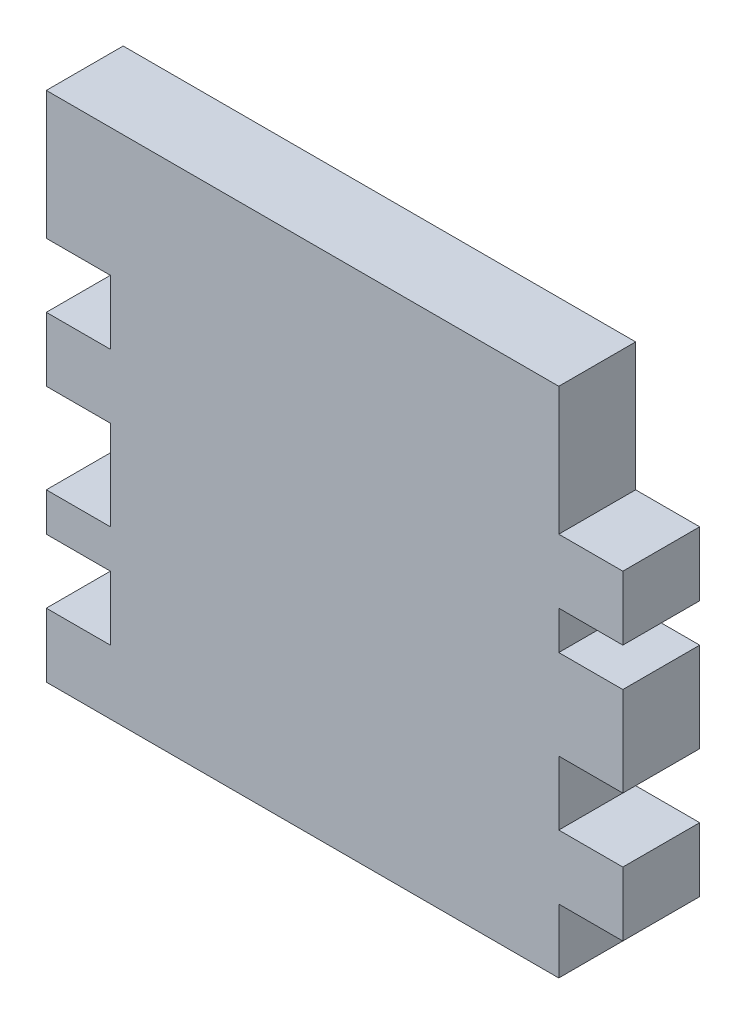
SolidWorks part; units mm, degrees
ref_plane "Front Plane" through (0, 0, 0) normal (0, 0, 1) x (1, 0, 0)
ref_plane "Top Plane" through (0, 0, 0) normal (0, 1, 0) x (1, 0, 0)
ref_plane "Right Plane" through (0, 0, 0) normal (1, 0, 0) x (0, 0, -1)
sketch "Sketch1" plane through (0, 0, 0) normal (0, 0, 1) x (1, 0, 0)
  line L1 (-18.4337, 17.4849) -> (26.5663, 17.4849)
  line L2 (-18.4337, 17.4849) -> (-18.4337, -22.5151)
  line L3 (-18.4337, -22.5151) -> (26.5663, -22.5151)
  line L4 (26.5663, 17.4849) -> (26.5663, -22.5151)
  dimension "D1" = 45
  dimension "D2" = 40
extrude "Boss-Extrude1" add sketch "Sketch1" along normal blind 6 contours L2 L1 L4 L3
sketch "Sketch2" plane through (0, 0, 6) normal (0, 0, 1) x (1, 0, 0)
  line L0 (-18.4337, 17.4849) -> (-18.4337, -22.5151) construction
  line L1 (-18.4337, 7.4849) -> (-13.4337, 7.4849)
  line L2 (-18.4337, 7.4849) -> (-18.4337, 2.4849)
  line L3 (-18.4337, 2.4849) -> (-13.4337, 2.4849)
  line L4 (-13.4337, 7.4849) -> (-13.4337, 2.4849)
  line L5 (-18.4337, 17.4849) -> (26.5663, 17.4849) construction
  line L6 (-18.4337, -2.5151) -> (-13.4337, -2.5151)
  line L7 (-18.4337, -2.5151) -> (-18.4337, -9.5151)
  line L8 (-18.4337, -9.5151) -> (-13.4337, -9.5151)
  line L9 (-13.4337, -2.5151) -> (-13.4337, -9.5151)
  line L10 (-18.4337, -12.5151) -> (-13.4337, -12.5151)
  line L11 (-18.4337, -12.5151) -> (-18.4337, -17.5151)
  line L12 (-18.4337, -17.5151) -> (-13.4337, -17.5151)
  line L13 (-13.4337, -12.5151) -> (-13.4337, -17.5151)
  line L14 (-18.4337, -22.5151) -> (26.5663, -22.5151) construction
  dimension "D1" = 5
  dimension "D2" = 5
  dimension "D3" = 5
  dimension "D4" = 5
  dimension "D5" = 10
  dimension "D6" = 5
  dimension "D7" = 5
  dimension "D8" = 5
  dimension "D9" = 7
extrude "Cut-Extrude1" cut sketch "Sketch2" against normal blind 6 contours L2 L1 L4 L3 | L7 L6 L9 L8 | L11 L10 L13 L12
sketch "Sketch3" plane through (0, 0, 6) normal (0, 0, 1) x (1, 0, 0)
  line L0 (26.5663, 17.4849) -> (26.5663, -22.5151) construction
  line L1 (21.5663, 2.4849) -> (26.5663, 2.4849)
  line L2 (21.5663, 2.4849) -> (21.5663, 7.4849)
  line L3 (21.5663, 7.4849) -> (26.5663, 7.4849)
  line L4 (26.5663, 2.4849) -> (26.5663, 7.4849)
  line L6 (26.5663, -0.5151) -> (21.5663, -0.5151)
  line L7 (26.5663, -0.5151) -> (26.5663, -7.5151)
  line L8 (26.5663, -7.5151) -> (21.5663, -7.5151)
  line L9 (21.5663, -0.5151) -> (21.5663, -7.5151)
  line L10 (26.5663, -12.5151) -> (21.5663, -12.5151)
  line L11 (26.5663, -12.5151) -> (26.5663, -17.5151)
  line L12 (26.5663, -17.5151) -> (21.5663, -17.5151)
  line L13 (21.5663, -12.5151) -> (21.5663, -17.5151)
  line L16 (21.5663, 7.4849) -> (26.5663, 7.4849)
  line L17 (21.5663, 7.4849) -> (21.5663, 17.4849)
  line L18 (21.5663, 17.4849) -> (26.5663, 17.4849)
  line L19 (26.5663, 7.4849) -> (26.5663, 17.4849)
  line L20 (21.5663, -0.5151) -> (26.5663, -0.5151)
  line L21 (21.5663, -0.5151) -> (21.5663, 2.4849)
  line L22 (21.5663, 2.4849) -> (26.5663, 2.4849)
  line L23 (26.5663, -0.5151) -> (26.5663, 2.4849)
  line L24 (21.5663, -12.5151) -> (26.5663, -12.5151)
  line L25 (21.5663, -12.5151) -> (21.5663, -7.5151)
  line L26 (21.5663, -7.5151) -> (26.5663, -7.5151)
  line L27 (26.5663, -12.5151) -> (26.5663, -7.5151)
  line L28 (21.5663, -17.5151) -> (26.5663, -17.5151)
  line L29 (21.5663, -17.5151) -> (21.5663, -22.5151)
  line L30 (21.5663, -22.5151) -> (26.5663, -22.5151)
  line L31 (26.5663, -17.5151) -> (26.5663, -22.5151)
  line M19 (-18.4337, -22.5151) -> (26.5663, -22.5151)
  line M20 (26.5663, -22.5151) -> (26.5663, 17.4849)
  line M21 (26.5663, 17.4849) -> (-18.4337, 17.4849)
  dimension "D1" = 5
  dimension "D4" = 5
  dimension "D6" = 5
  dimension "D7" = 7
extrude "Cut-Extrude3" cut sketch "Sketch3" against normal blind 6 contours L10 L13 L12 M20 | L6 L9 L8 M20 | L3 L2 L1 M20 region at (24.0663, 4.9849, 6) region at (24.0663, -4.0151, 6) region at (24.0663, -15.0151, 6)
extrude "Boss-Extrude3" add sketch "Sketch3<4>" against normal blind 6 contours L3 L2 L1 M20 | L6 L9 L8 M20 | L10 L13 L12 M20 region at (24.0663, 4.9849, 6) region at (24.0663, -4.0151, 6) region at (24.0663, -15.0151, 6)
sketch "Sketch3<4>" plane through (0, 0, 6) normal (0, 0, 1) x (1, 0, 0) same geometry as "Sketch3"
extrude "Cut-Extrude4" cut sketch "Sketch3<5>" against normal blind 6 contours L17 L3 M20 M21 | L21 L6 L1 M20 | L25 L10 L8 M20 | L12 L29 M19 M20 region at (24.0663, 0.9849, 6) region at (24.0663, 12.4849, 6) region at (24.0663, -10.0151, 6) region at (24.0663, -20.0151, 6)
sketch "Sketch3<5>" plane through (0, 0, 6) normal (0, 0, 1) x (1, 0, 0) same geometry as "Sketch3"
